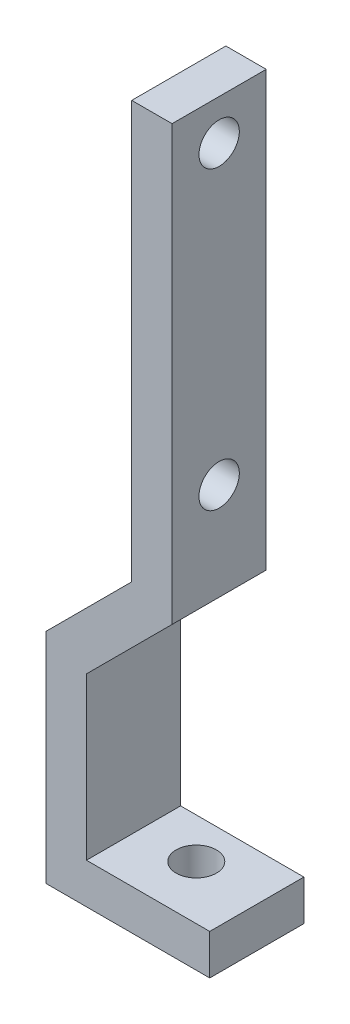
SolidWorks part; units mm, degrees
ref_plane "前视基准面" through (0, 0, 0) normal (0, 0, 1) x (1, 0, 0)
ref_plane "上视基准面" through (0, 0, 0) normal (0, 1, 0) x (1, 0, 0)
ref_plane "右视基准面" through (0, 0, 0) normal (1, 0, 0) x (0, 0, -1)
sketch "草图1" plane through (0, 0, 0) normal (0, 0, 1) x (1, 0, 0)
  line L0 (-3.6411, 21.9867) -> (-3.6411, -9.0133)
  line L1 (-3.6411, -9.0133) -> (-10.005, -15.3772)
  line L2 (-10.005, -15.3772) -> (-10.005, -31.6199)
  line L3 (-10.005, -31.6199) -> (2.1589, -31.6199)
  line L4 (2.1589, -31.6199) -> (2.1589, -28.6199)
  line L5 (2.1589, -28.6199) -> (-7.005, -28.6199)
  line L6 (-7.005, -28.6199) -> (-7.005, -16.6199)
  line L7 (-7.005, -16.6199) -> (-0.6411, -10.2559)
  line L8 (-0.6411, -10.2559) -> (-0.6411, 21.9867)
  line L9 (-0.6411, 21.9867) -> (-3.6411, 21.9867)
  line L10 (-2.8411, -28.6199) -> (-2.8411, -31.6199)
  line L11 (-4.3411, -28.6199) -> (-4.3411, -31.6199)
  line L12 (-1.3411, -28.6199) -> (-1.3411, -31.6199)
  dimension "D1" = 3
  dimension "D2" = 3
  dimension "D3" = 3
  dimension "D4" = 3
  dimension "D5" = 31
  dimension "D6" = 12
  dimension "D7" = 9
  dimension "D8" = 1.5
  dimension "D9" = 1.5
  dimension "D10" = 0.8
  dimension "D11" = 5
extrude "凸台-拉伸1" add sketch "草图1" along normal blind 7 contours L11 L5 L6 L7 L8 L9 L0 L1 L2 L3 | L12 L5 L10 L3 | L5 L11 L3 L10 | L5 L12 L3 L4 region at (-2.1411, 21.4425, 0) region at (-3.5911, -30.1199, 0) region at (-2.0911, -30.1199, 0) region at (0.4089, -30.1199, 0)
sketch "草图2" plane through (-3.6411, 0, 0) normal (-1, 0, 0) x (0, 0, 1)
  line L0 (7, 21.9867) -> (0, 21.9867) construction
  line L1 (0, 21.9867) -> (0, -9.0133) construction
  circle A0 centre (3.5, 18.9867) radius 1.5
  circle A1 centre (3.5, -3.0133) radius 1.5
  dimension "D2" = 3
  dimension "D3" = 3
  dimension "D1" = 3
  dimension "D4" = 22
  dimension "D5" = 3.5
  dimension "D6" = 3.5
extrude "切除-拉伸2" cut sketch "草图2" against normal blind 7
sketch "草图4" plane through (0, -28.6199, 0) normal (0, 1, 0) x (1, 0, 0)
  line L0 (2.1589, 0) -> (-7.005, 0) construction
  line L1 (2.1589, -7) -> (2.1589, 0) construction
  circle A0 centre (-2.8411, -3) radius 1.5
  dimension "D2" = 3
  dimension "D1" = 3
  dimension "D3" = 5
extrude "切除-拉伸3" cut sketch "草图4" against normal blind 7
